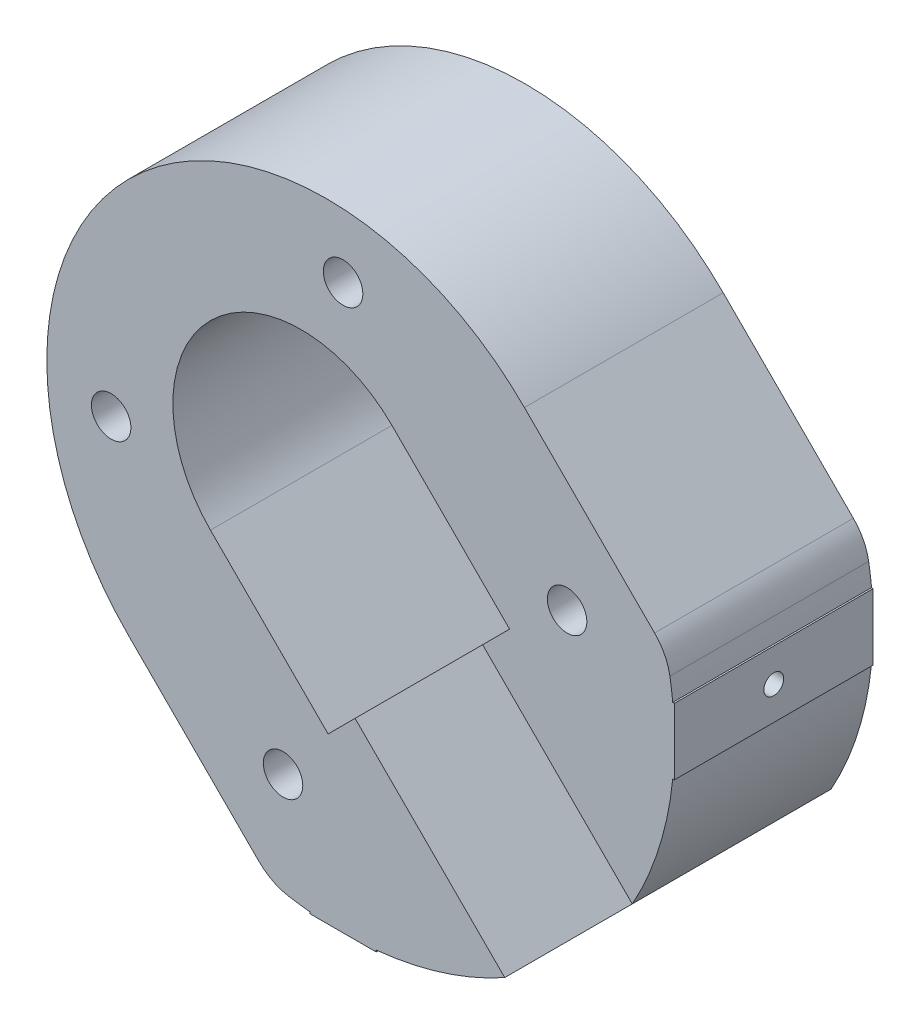
SolidWorks part; units mm, degrees
ref_plane "Front Plane" through (0, 0, 0) normal (0, 0, 1) x (1, 0, 0)
ref_plane "Top Plane" through (0, 0, 0) normal (0, 1, 0) x (1, 0, 0)
ref_plane "Right Plane" through (0, 0, 0) normal (1, 0, 0) x (0, 0, -1)
ref_axis "Z" through (0, 0, 33.5996) along (0, 0, -1)
ref_axis "X" through (56.0652, 0, 0) along (-1, 0, 0)
ref_axis "Y" through (0, -54.2845, 0) along (0, 1, 0)
sketch "Sketch1" plane through (0, 0, 0) normal (0, 0, 1) x (1, 0, 0)
  line L0 (5, -50) -> (-5, -50)
  line L1 (50, 5) -> (50, -5)
  line L2 (56.0652, 0) -> (-1.1166, 0) construction
  line L3 (0, -54.2845) -> (0, 1.1167) construction
  line L4 (61.712, 0) -> (50, 0) construction
  line L5 (0, -50) -> (0, -57.4075) construction
  line L6 (50, -5) -> (49.7494, -5)
  line L7 (5, -49.7494) -> (5, -50)
  line L10 (65.572, -65.572) -> (0, 0) construction
  line L20 (-5, -50) -> (-5, -49.7494)
  line L21 (49.7494, 5) -> (50, 5)
  line L22 (24.3964, -43.6442) -> (1.8103, -21.058)
  line L23 (43.6442, -24.3964) -> (21.058, -1.8103)
  line L25 (1.8103, -21.058) -> (-2.2604, -25.1287)
  line L26 (-2.2604, -25.1287) -> (-20.0175, -7.3715)
  line L27 (21.058, -1.8103) -> (25.1287, 2.2604)
  line L28 (25.1287, 2.2604) -> (7.3715, 20.0175)
  line L29 (-12.6985, -47.012) -> (-32.3444, -27.3661)
  line L30 (47.012, 12.6985) -> (27.3661, 32.3444)
  circle A0 centre (0, 0) radius 50 construction
  circle A1 centre (0, 0) radius 3.535 construction
  arc A2 (49.7494, -5) -> (5, -49.7494) centre (0, 0) cw construction
  arc A6 (49.7494, 5) -> (49.3214, 8.2098) centre (0, 0) ccw
  arc A7 (5, -49.7494) -> (24.3964, -43.6442) centre (0, 0) ccw
  arc A8 (49.7494, -5) -> (43.6442, -24.3964) centre (0, 0) cw
  arc A9 (7.3715, 20.0175) -> (-20.0175, -7.3715) centre (-6.323, 6.323) ccw
  arc A10 (-8.2098, -49.3214) -> (-12.6985, -47.012) centre (-6.8523, -41.1658) cw
  arc A12 (-8.2098, -49.3214) -> (-5, -49.7494) centre (0, 0) ccw
  arc A13 (35.3553, -35.3553) -> (-8.2098, -49.3214) centre (0, 0) ccw construction
  arc A15 (49.3214, 8.2098) -> (47.012, 12.6985) centre (41.1658, 6.8523) ccw
  arc A17 (49.3214, 8.2098) -> (35.3553, -35.3553) centre (0, 0) ccw construction
  arc A18 (27.3661, 32.3444) -> (-32.3444, -27.3661) centre (-2.4891, 2.4891) ccw
  dimension "D1" = 100
  dimension "D2" = 7.07
  dimension "D3" = 10
  dimension "D4" = 45
extrude "Boss-Extrude1" add sketch "Sketch1" against normal blind 15 and the other way blind 15
sketch "Sketch2" plane through (0, -50, 0) normal (0, 1, 0) x (1, 0, 0)
  line L0 (-57.5886, 0) -> (57.5886, 0) construction
  line L1 (0, -20.5521) -> (0, 20.5521) construction
  circle A0 centre (0, 0) radius 1.5
  dimension "D1" = 3
extrude "Cut-Extrude1" cut sketch "Sketch2" along normal blind 24
sketch "Sketch3" plane through (50, 0, 0) normal (1, 0, 0) x (0, 0, -1)
  circle A0 centre (0, 0) radius 1.5
  dimension "D1" = 3
extrude "Cut-Extrude2" cut sketch "Sketch3" against normal blind 24
sketch "Sketch5" plane through (0, 0, 0) normal (0, 0, 1) x (1, 0, 0)
  line L0 (0, 0) -> (0, -66.8046) construction
  dimension "D1" = 66.8046
ref_plane "Vert" through (0, 0, 0) normal (0.7071, 0.7071, 0) x (0, 0, -1)
sketch "Sketch6" plane through (0, 0, 0) normal (0, 0, 1) x (1, 0, 0)
  line L0 (0, 0) -> (-9.0587, -33.8074) construction
  line L1 (0, 0) -> (18.8244, -18.8244) construction
  line L2 (0, -54.2845) -> (0, 1.1167) construction
  line L3 (0, 0) -> (-35, 0) construction
  circle A0 centre (-9.0587, -33.8074) radius 2.9766
  circle A1 centre (-35, 0) radius 2.9766
  circle A2 centre (0, 35) radius 2.9766
  circle A3 centre (33.8074, 9.0587) radius 2.9766
  dimension "D4" = 5.9531
  dimension "D1" = 35
  dimension "D2" = 45
  dimension "D3" = 60
extrude "Cut-Extrude4" cut sketch "Sketch6" along normal through all
equation "\"EyeDiameter\" = 99.60916292"
equation "\"BasePlaneDistance\" = \"EyeDiameter\"/2+\"L2Thickness\"+\"EyeClearance\""
equation "\"EyeClearance\" = 2"
equation "\"EyeOD\"= \"EyeDiameter\""
equation "\"D2@Sketch1\"= 7.07"
equation "\"pinHoleDiameter\"= 3"
equation "\"D1@Sketch2\"=\"pinHoleDiameter\""
equation "\"D1@Sketch3\"=\"pinHoleDiameter\""
equation "\"D1@Sketch5\"=\"BasePlaneDistance\""
equation "\"L2_ID\" = 20"
equation "\"vx\" = 50"
equation "\"vy\" = 10"
equation "\"vz\" = 100"
equation "\"parametric_end\" = 1"
equation "\"Rw_3_xx\" = -(\"vz\")/sqr((\"vx\")^2 + (\"vz\")^2)"
equation "\"Rw_3_xy\" = 0"
equation "\"Rw_3_xz\" = (\"vx\")/sqr((\"vx\")^2 + (\"vz\")^2)"
equation "\"Rw_3_zx\" = (\"vx\")/sqr((\"vx\")^2 + (\"vy\")^2 + (\"vz\")^2)"
equation "\"Rw_3_zy\" = (\"vy\")/sqr((\"vx\")^2 + (\"vy\")^2 + (\"vz\")^2)"
equation "\"Rw_3_zz\" = (\"vz\")/sqr((\"vx\")^2 + (\"vy\")^2 + (\"vz\")^2)"
equation "\"Rw_3_yx\" = (\"vx\")*(\"vy\")/sqr((\"vx\")^4 + (\"vx\")^2*(\"vy\")^2 + 2*(\"vx\")^2*(\"vz\")^2 + (\"vy\")^2*(\"vz\")^2 + (\"vz\")^4)"
equation "\"Rw_3_yy\" = -sqr((\"vx\")^2 + (\"vz\")^2)/sqr((\"vx\")^2 + (\"vy\")^2 + (\"vz\")^2)"
equation "\"Rw_3_yz\" = (\"vy\")*(\"vz\")/sqr((\"vx\")^4 + (\"vx\")^2*(\"vy\")^2 + 2*(\"vx\")^2*(\"vz\")^2 + (\"vy\")^2*(\"vz\")^2 + (\"vz\")^4)"
equation "\"O2Targx\" = -\"BasePlaneDistance\"*(\"vx\")*(\"vy\")/sqr((\"vx\")^4 + (\"vx\")^2*(\"vy\")^2 + 2*(\"vx\")^2*(\"vz\")^2 + (\"vy\")^2*(\"vz\")^2 + (\"vz\")^4)"
equation "\"O2Targy\" = \"BasePlaneDistance\"*sqr((\"vx\")^2 + (\"vz\")^2)/sqr((\"vx\")^2 + (\"vy\")^2 + (\"vz\")^2)"
equation "\"O2Targz\" = -\"BasePlaneDistance\"*(\"vy\")*(\"vz\")/sqr((\"vx\")^4 + (\"vx\")^2*(\"vy\")^2 + 2*(\"vx\")^2*(\"vz\")^2 + (\"vy\")^2*(\"vz\")^2 + (\"vz\")^4)"
equation "\"O2Targx_0\" = -(\"BasePlaneDistance\")*sqr((\"vx\")^2 + (\"vz\")^2)/sqr((\"vx\")^2 + (\"vy\")^2 + (\"vz\")^2)"
equation "\"O2Targy_0\" = -(\"BasePlaneDistance\")*(\"vy\")*(\"vz\")/sqr((\"vx\")^4 + (\"vx\")^2*(\"vy\")^2 + 2*(\"vx\")^2*(\"vz\")^2 + (\"vy\")^2*(\"vz\")^2 + (\"vz\")^4)"
equation "\"O2Targz_0\" = (\"BasePlaneDistance\")*(\"vx\")*(\"vy\")/sqr((\"vx\")^4 + (\"vx\")^2*(\"vy\")^2 + 2*(\"vx\")^2*(\"vz\")^2 + (\"vy\")^2*(\"vz\")^2 + (\"vz\")^4) + (\"BasePlaneDistance\")"
equation "\"theta2_s1\" = arcsin(((\"BasePlaneDistance\") - (\"O2Targz_0\"))/(\"BasePlaneDistance\")) + pi"
equation "\"theta2_s2\" = -arcsin(((\"BasePlaneDistance\") - (\"O2Targz_0\"))/(\"BasePlaneDistance\"))"
equation "\"theta1_s1\" = arcsin((\"O2Targy_0\")/((\"BasePlaneDistance\")*cos((\"Theta2\")))) + pi"
equation "\"theta1_s2\" = -arcsin((\"O2Targy_0\")/((\"BasePlaneDistance\")*cos((\"Theta2\"))))"
equation "\"theta1_s3\" = -arccos(-(\"O2Targx_0\")/((\"BasePlaneDistance\")*cos((\"Theta2\")))) + 2*pi"
equation "\"theta1_s4\" = arccos(-(\"O2Targx_0\")/((\"BasePlaneDistance\")*cos((\"Theta2\"))))"
equation "\"Theta1\" = \"theta1_s2\" 'so far, theta1_s1 and theta1_s4 have agreed, and they agree with the sw constraint solver"
equation "\"Theta2\" = \"theta2_s2\""
equation "\"o2_x\" = -(\"BasePlaneDistance\")*cos((\"Theta1\"))*cos((\"Theta2\"))"
equation "\"o2_y\" = -(\"BasePlaneDistance\")*sin((\"Theta1\"))*cos((\"Theta2\"))"
equation "\"o2_z\" = (\"BasePlaneDistance\")*(sin((\"Theta2\")) + 1)"
equation "\"o1_x\" = (\"BasePlaneDistance\")*sin((\"Theta1\"))"
equation "\"o1_y\" = -(\"BasePlaneDistance\")*cos((\"Theta1\"))"
equation "\"o1_z\" = (\"BasePlaneDistance\")"
equation "\"Actuator1_Theta\" = atn(\"vx\"/\"vz\") 'ik solution for the single link joint"
equation "\"Actuator2_Theta\" = \"Theta1\"  'ik solution for the double link joint"
equation "\"MotorBaseThickness\" = 3 "
equation "\"BaseThickness\" = 3 "
equation "\"EncoderToMagnetAirgap\" = 1 'Encoder to magnet airgap"
equation "\"EncoderHeight\" = 1.192  'Height of the encoder"
equation "\"MagnetThickness\" = 0.5  'Magnet thickness"
equation "\"pcb_thickness\" = 1.6  'Thickness of the PCB"
equation "\"pcb_outer_diameter\" = 32 'the OD of the pcb"
equation "\"shaft_diameter\" = 4"
equation "\"L2Thickness\" = 3.75 * \"shaft_diameter\""
equation "\"D1@Cut-Extrude2\"=\"shaft_diameter\"*6"
equation "\"D1@Cut-Extrude1\"=\"shaft_diameter\"*6"
